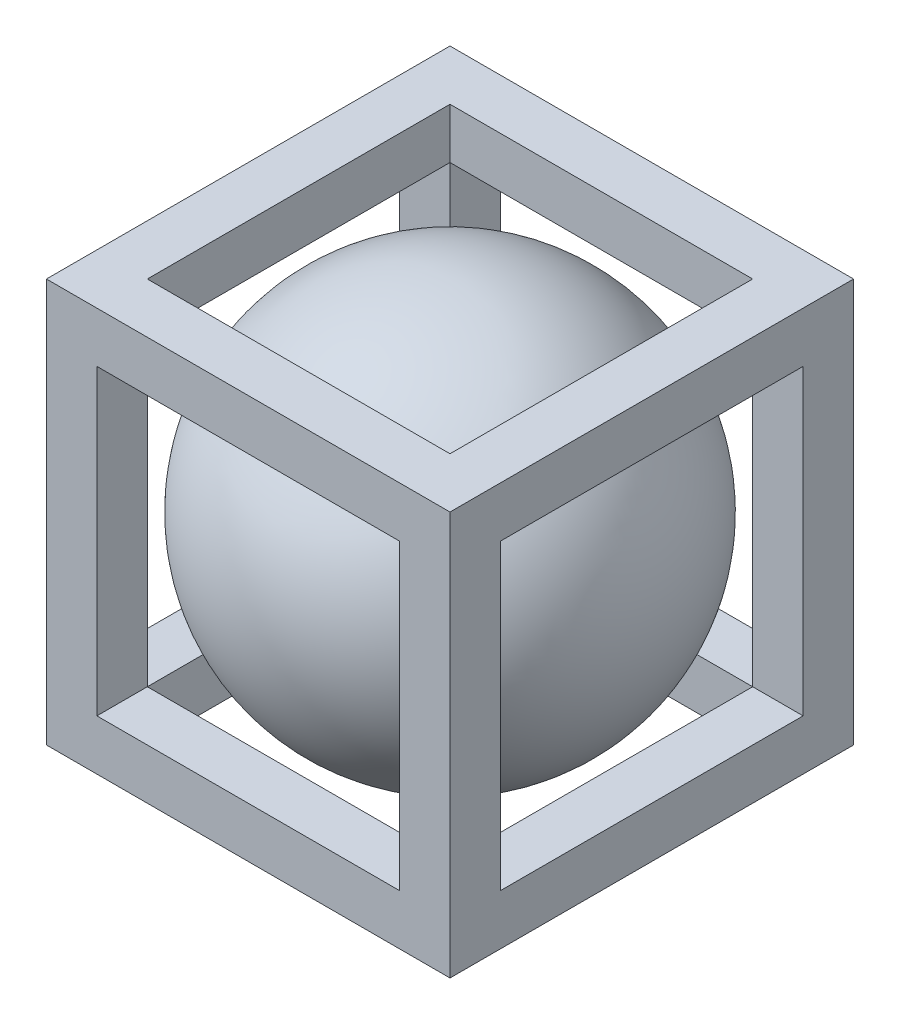
SolidWorks part; units mm, degrees
ref_plane "Front Plane" through (0, 0, 0) normal (0, 0, 1) x (1, 0, 0)
ref_plane "Top Plane" through (0, 0, 0) normal (0, 1, 0) x (1, 0, 0)
ref_plane "Right Plane" through (0, 0, 0) normal (1, 0, 0) x (0, 0, -1)
sketch "Sketch1" plane through (0, 0, 0) normal (0, 0, 1) x (1, 0, 0)
  line L1 (-20, -20) -> (20, -20)
  line L2 (-20, -20) -> (-20, 20)
  line L3 (-20, 20) -> (20, 20)
  line L4 (20, -20) -> (20, 20)
  line L5 (-20, -20) -> (20, 20) construction
  line L6 (-20, 20) -> (20, -20) construction
  point P0 (0, 0)
  dimension "D1" = 40
  dimension "D2" = 40
extrude "Boss-Extrude1" add sketch "Sketch1" along normal blind 20 and the other way blind 20
sketch "Sketch2" plane through (0, 0, 0) normal (0, 0, 1) x (1, 0, 0)
  line L1 (-15, -15) -> (15, -15)
  line L2 (-15, -15) -> (-15, 15)
  line L3 (-15, 15) -> (15, 15)
  line L4 (15, -15) -> (15, 15)
  line L5 (-15, -15) -> (15, 15) construction
  line L6 (-15, 15) -> (15, -15) construction
  point P0 (0, 0)
  dimension "D1" = 30
  dimension "D2" = 30
extrude "Cut-Extrude1" cut sketch "Sketch2" against normal through all both and the other way through all
sketch "Sketch3" plane through (0, 0, 0) normal (0, 1, 0) x (1, 0, 0)
  line L1 (-15, -15) -> (15, -15)
  line L2 (-15, -15) -> (-15, 15)
  line L3 (-15, 15) -> (15, 15)
  line L4 (15, -15) -> (15, 15)
  line L5 (-15, -15) -> (15, 15) construction
  line L6 (-15, 15) -> (15, -15) construction
  point P0 (0, 0)
  point P5 (0, 0)
  dimension "D1" = 30
  dimension "D2" = 30
extrude "Cut-Extrude2" cut sketch "Sketch3" against normal through all both and the other way through all
sketch "Sketch4" plane through (0, 0, 0) normal (1, 0, 0) x (0, 0, -1)
  line L1 (-15, -15) -> (15, -15)
  line L2 (-15, -15) -> (-15, 15)
  line L3 (-15, 15) -> (15, 15)
  line L4 (15, -15) -> (15, 15)
  line L5 (-15, -15) -> (15, 15) construction
  line L6 (-15, 15) -> (15, -15) construction
  point P0 (0, 0)
  point P5 (0, 0)
  dimension "D1" = 30
  dimension "D2" = 30
extrude "Cut-Extrude3" cut sketch "Sketch4" against normal through all both and the other way through all
sketch "Sketch5" plane through (0, 0, 0) normal (0, 0, 1) x (1, 0, 0)
  line L0 (-20, 0) -> (20, 0)
  arc A0 (20, 0) -> (-20, 0) centre (0, 0) ccw
  point P4 (0, 0)
  dimension "D1" = 40
revolve "Revolve1" add sketch "Sketch5" angle 360 about L0
